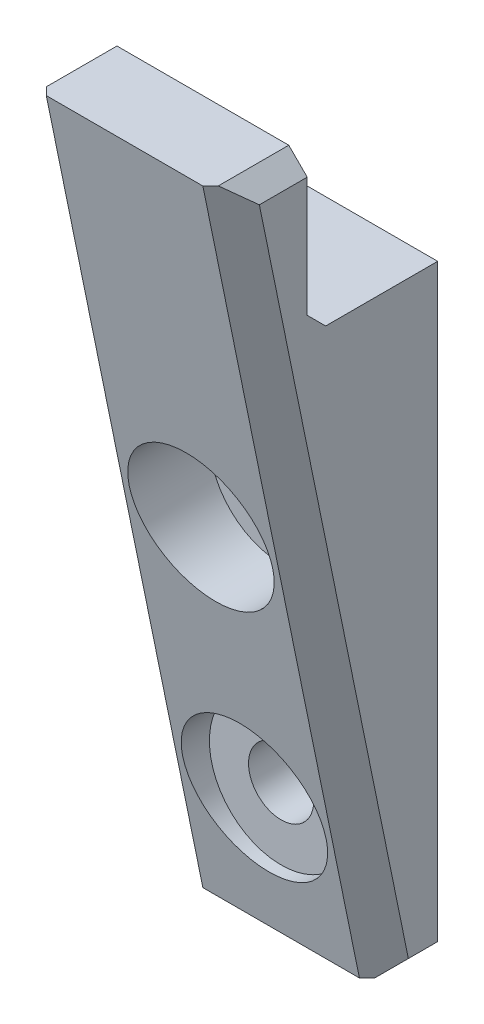
SolidWorks part; units mm, degrees
ref_plane "Alzado" through (0, 0, 0) normal (0, 0, 1) x (1, 0, 0)
ref_plane "Planta" through (0, 0, 0) normal (0, 1, 0) x (1, 0, 0)
ref_plane "Vista lateral" through (0, 0, 0) normal (1, 0, 0) x (0, 0, -1)
sketch "Croquis1" plane through (0, 0, 0) normal (0, 0, 1) x (1, 0, 0)
  line L1 (8, 45) -> (-8, 45)
  line L2 (8, 45) -> (8, -45)
  line L3 (8, -45) -> (-8, -45)
  line L4 (-8, 45) -> (-8, -45)
  line L5 (8, 45) -> (-8, -45) construction
  line L6 (8, -45) -> (-8, 45) construction
  point P0 (0, 0)
  dimension "D1" = 16
  dimension "D2" = 90
extrude "Base" add sketch "Croquis1" along normal blind 16
sketch "Croquis2" plane through (0, 0, 16) normal (0, 0, 1) x (1, 0, 0)
  line L0 (0, -45) -> (0, -35) construction
  line L1 (-8, -45) -> (8, -45) construction
  line L2 (0, -35) -> (0, -15) construction
  line L3 (0, -15) -> (0, 13.58) construction
  line L4 (8, -45) -> (8, 45) construction
  line L5 (8, 13.58) -> (-8, 13.58)
  line L6 (8, 13.58) -> (8, 45)
  line L7 (8, 45) -> (-8, 45)
  line L8 (-8, 13.58) -> (-8, 45)
  circle A0 centre (0, -35) radius 2.5
  circle A1 centre (0, -15) radius 2.5
  dimension "D1" = 20
  dimension "D2" = 28.58
extrude "Barrenos" cut sketch "Croquis2" against normal through all
sketch "Croquis3" plane through (0, 0, 16) normal (0, 0, 1) x (1, 0, 0)
  line L0 (-6.5858, 13.58) -> (-8, 12.1658)
  line L1 (-8, 13.58) -> (8, 13.58) construction
  line L2 (-8, 13.58) -> (-8, -45) construction
  line L3 (6.5858, 13.58) -> (8, 12.1658)
  line L4 (8, -45) -> (8, 13.58) construction
  line L5 (8, 12.1658) -> (8, 13.58)
  line L6 (8, 13.58) -> (6.5858, 13.58)
  line L7 (-6.5858, 13.58) -> (-8, 13.58)
  line L8 (-8, 13.58) -> (-8, 12.1658)
  line L9 (8, -15.71) -> (13.1228, -15.71) construction
  line L10 (-8, -45) -> (-8, -43.5858)
  line L11 (-6.5858, -45) -> (-8, -45)
  line L12 (8, -45) -> (6.5858, -45)
  line L13 (8, -43.5858) -> (8, -45)
  line L14 (6.5858, -45) -> (8, -43.5858)
  line L15 (-6.5858, -45) -> (-8, -43.5858)
  dimension "D1" = 135
  dimension "D2" = 2
  dimension "D3" = 135
  dimension "D4" = 2
extrude "Cortar-Extruir1" cut sketch "Croquis3" against normal through all
sketch "Croquis4" plane through (-8, 0, 0) normal (-1, 0, 0) x (0, 0, 1)
  line L6 (10, 2.9942) -> (8.5858, 1.58)
  line L7 (0, 13.58) -> (10, 13.58)
  line L8 (0, 13.58) -> (0, 1.58)
  line L9 (0, 1.58) -> (10, 1.58)
  line L10 (10, 13.58) -> (10, 1.58)
  line M6 (0, 12.1658) -> (0, -43.5858)
  line M9 (16, 12.1658) -> (0, 12.1658)
  dimension "D1" = 10
  dimension "D2" = 12
  dimension "D3" = 45
  dimension "D4" = 2
extrude "Cortar-Extruir2" cut sketch "Croquis4" against normal through all contours L10 L7 L8 M9 | L10 L9 L6 M9 M6 region at (-8, 6.9189, 4.9568) region at (-8, 12.8729, 5)
sketch "Croquis6" plane through (-8, 0, 0) normal (-1, 0, 0) x (0, 0, 1)
  line L0 (8, -45) -> (0, -45)
  line L3 (0, -45) -> (16, -45) construction
  line L4 (0, -45) -> (4, -45)
  line L5 (4, -45) -> (16, 13.58)
  line L6 (16, 13.58) -> (4, 13.58)
  line L7 (16, 13.58) -> (16, -45)
  line L8 (16, -45) -> (4, -45)
  line L9 (4, 13.58) -> (4, -45)
  line M11 (0, -43.5858) -> (16, -43.5858)
  line M12 (16, -43.5858) -> (16, 12.1658)
  line M13 (16, 12.1658) -> (10, 12.1658)
extrude "Cortar-Extruir4" cut sketch "Croquis6" against normal through all contours L7 L5 M13 | L5 M11 M12 M13 | L8 L7 L5 L0 M11 region at (-8, -44.2958, 10.0721) region at (-8, -24.5533, 12.0942) region at (-8, 12.6372, 15.9034)
chamfer "Chaflán2" distance 2 angle 45 2 edges at (-8, -15.71, 10) (8, -15.71, 10)
ref_plane "Plano1" through (0, 0, 16) normal (0, 0, 1) x (1, 0, 0)
sketch "Croquis8" plane through (0, 0, 16) normal (0, 0, 1) x (1, 0, 0)
  circle A0 centre (0, -15) radius 5.5
  circle A1 centre (0, -35) radius 5.5
  dimension "D1" = 11
  dimension "D2" = 11
extrude "Cortar-Extruir6" cut sketch "Croquis8" against normal blind 12
